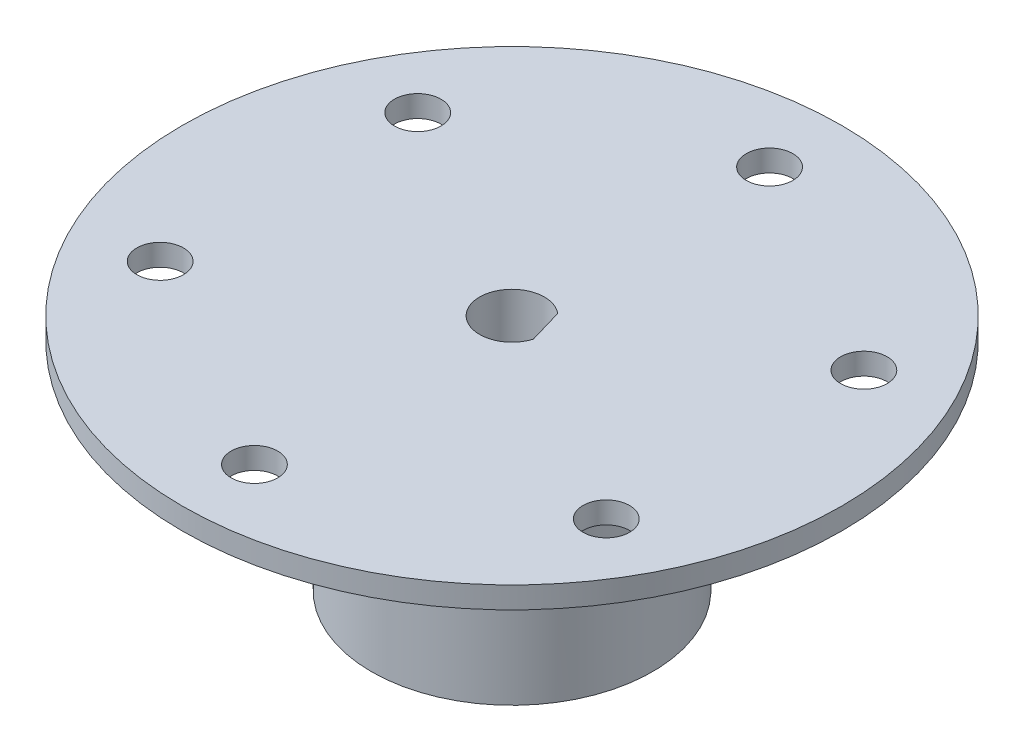
SolidWorks part; units mm, degrees
ref_plane "Front" through (0, 0, 0) normal (0, 0, 1) x (1, 0, 0)
ref_plane "Top" through (0, 0, 0) normal (0, 1, 0) x (1, 0, 0)
ref_plane "Right" through (0, 0, 0) normal (1, 0, 0) x (0, 0, -1)
sketch "Sketch1" plane through (0, 0, 0) normal (0, 1, 0) x (1, 0, 0)
  circle A1 centre (0, 0) radius 30.48
  circle A2 centre (0, -23.8125) radius 2.1526
  circle A3 centre (20.6222, -11.9062) radius 2.1526
  circle A4 centre (20.6222, 11.9063) radius 2.1526
  circle A5 centre (0, 23.8125) radius 2.1526
  circle A6 centre (-20.6222, 11.9062) radius 2.1527
  circle A7 centre (-20.6222, -11.9062) radius 2.1527
extrude "Boss-Extrude1" add sketch "Sketch1" along normal blind 2
sketch "Sketch2" plane through (0, 2, 0) normal (0, 1, 0) x (1, 0, 0)
  line L0 (2.8645, -0.8913) -> (1.932, 2.295)
  circle A0 centre (0, 0) radius 3
  dimension "D1" = 3.32
extrude "Cut-Extrude1" cut sketch "Sketch2" against normal blind 10 contours L0 A0 region at (-0.1078, 2, 0.0316)
sketch "Sketch3" plane through (0, 0, 0) normal (0, -1, 0) x (1, 0, 0)
  line L0 (1.932, -2.295) -> (2.8645, 0.8913)
  circle A0 centre (0, 0) radius 13
  circle A1 centre (0, 0) radius 3.1104
  arc M1 (1.932, -2.295) -> (2.8645, 0.8913) centre (0, 0) cw
  line M2 (2.8645, 0.8913) -> (1.932, -2.295)
  dimension "D1" = 26
extrude "Boss-Extrude2" add sketch "Sketch3" along normal blind 20 contours A0 A1 | A1 M2 M1 region at (-12.6323, 0, 0) region at (-3.0224, 0, 0)
